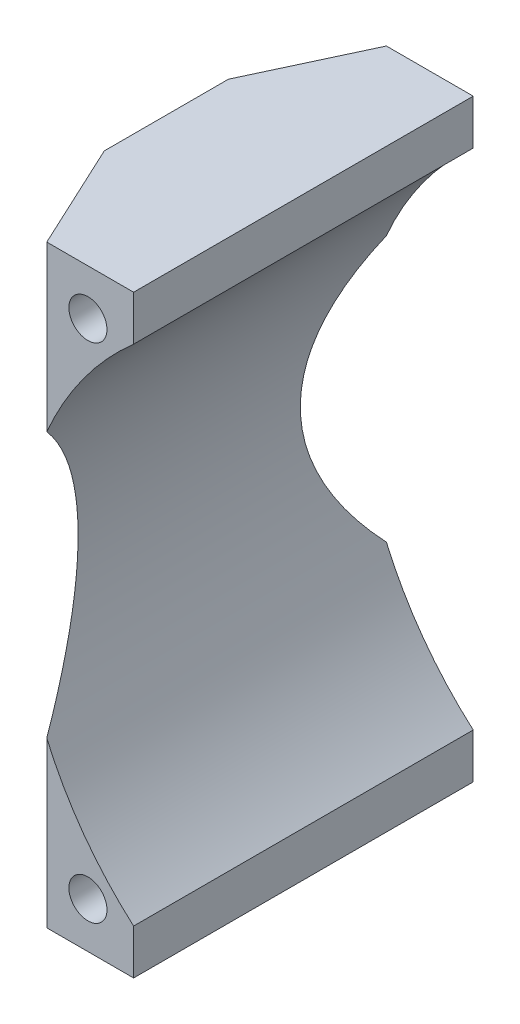
SolidWorks part; units mm, degrees
material "6061-T6 (SS)"
ref_plane "前视基准面" through (0, 0, 0) normal (0, 0, 1) x (1, 0, 0)
ref_plane "上视基准面" through (0, 0, 0) normal (0, 1, 0) x (1, 0, 0)
ref_plane "右视基准面" through (0, 0, 0) normal (1, 0, 0) x (0, 0, -1)
sketch "草图1" plane through (0, 0, 0) normal (0, 0, 1) x (1, 0, 0)
  line L1 (-8.5, 19.5) -> (0, 19.5)
  line L2 (-8.5, 19.5) -> (-8.5, -19.5)
  line L3 (-8.5, -19.5) -> (0, -19.5)
  line L4 (0, 19.5) -> (0, -19.5)
  dimension "D1" = 39
  dimension "D2" = 8.5
extrude "拉伸1" add sketch "草图1" along normal blind 22.3
sketch "草图2" plane through (0, 0, 22.3) normal (0, 0, 1) x (1, 0, 0)
  line L0 (0, 0) -> (14.5, 0) construction
  line L1 (-7.5, 0) -> (-8.5, 0) construction
  line L2 (-8.5, 19.5) -> (-8.5, -19.5) construction
  circle A0 centre (14.5, 0) radius 22
  dimension "D1" = 44
  dimension "D2" = 14.5
extrude "拉伸2" cut sketch "草图2" against normal up to surface (22.3 mm away) up to face at (-4.25, 0, 0)
chamfer "倒角1" [suppressed] distance 1 angle 45
sketch "草图3" plane through (0, 0, 22.3) normal (0, 0, 1) x (1, 0, 0)
  line L0 (-8.5, 19.5) -> (-8.5, -19.5) construction
  line L1 (-8.5, 9) -> (0, 9)
  line L2 (-8.5, 9) -> (-8.5, -19.5)
  line L3 (-8.5, -19.5) -> (0, -19.5)
  line L4 (0, 9) -> (0, -19.5)
  line L5 (0, -19.5) -> (0, -16.5454) construction
  line L6 (0, 19.5) -> (-8.5, 19.5) construction
  line L7 (-8.5, -19.5) -> (0, -19.5) construction
  dimension "D1" = 10.5
extrude "拉伸3" [suppressed] cut sketch "草图3" against normal up to surface (20.3 mm away)
sketch "草图4" plane through (0, 0, 22.3) normal (0, 0, 1) x (1, 0, 0)
  line L0 (-3, 16.5) -> (-3, 19.5) construction
  line L1 (0, 19.5) -> (-8.5, 19.5) construction
  line L2 (-3, 16.5) -> (-8.5, 16.5) construction
  line L3 (-8.5, 19.5) -> (-8.5, -19.5) construction
  line L4 (-3, 16.5) -> (-3, -16.5) construction
  circle A0 centre (-3, 16.5) radius 1.75
  dimension "D1" = 3.5
  dimension "D2" = 3
  dimension "D3" = 33
  dimension "D4" = 5.5
extrude "拉伸4" [suppressed] cut sketch "草图4" against normal up to surface (16.8 mm away)
hole_wizard "M3 螺纹孔1" positions "3D草图1" profile "草图5" tap size "M3" standard "GB"
sketch3d "3D草图1"
  point P0 (-3, 16.5, 22.3)
sketch "草图5" plane through (-3, 16.5, 22.3) normal (1, 0, 0) x (0, -1, 0)
  line L0 (0, 0) -> (0, 10.2511)
  line L1 (0, 10.2511) -> (1.25, 9.5)
  line L2 (1.25, 9.5) -> (1.25, 0)
  line L5 (1.25, 0) -> (0, 0)
  line L10 (0, 10.2511) -> (-1.25, 9.5) construction
  line L11 (0, -6.35) -> (0, 107.95) construction
  dimension "螺纹孔钻头直径" = 2.5
  dimension "螺纹孔钻头深度" = 9.5
  dimension "导头角度" = 118
cosmetic thread "孔螺蚊线3" parameters "D1"=8, "D2"=3
hole_wizard "M3 螺纹孔2" positions "3D草图2" profile "草图6" tap size "M3" standard "GB"
sketch3d "3D草图2"
  point P0 (-3, 16.5, 0)
sketch "草图6" plane through (-3, 16.5, 0) normal (1, 0, 0) x (0, 1, 0)
  line L0 (0, 0) -> (0, 10.2511)
  line L1 (0, 10.2511) -> (1.25, 9.5)
  line L2 (1.25, 9.5) -> (1.25, 0)
  line L5 (1.25, 0) -> (0, 0)
  line L10 (0, 10.2511) -> (-1.25, 9.5) construction
  line L11 (0, -6.35) -> (0, 107.95) construction
  dimension "螺纹孔钻头直径" = 2.5
  dimension "螺纹孔钻头深度" = 9.5
  dimension "导头角度" = 118
cosmetic thread "孔螺蚊线4" parameters "D1"=8, "D2"=3
hole_wizard "M3 螺纹孔3" positions "3D草图3" profile "草图7" tap size "M3" standard "GB"
sketch3d "3D草图3"
  point P0 (-3, -16.5, 22.3)
  point P3 (-3, -16.5, 0)
sketch "草图7" plane through (-3, -16.5, 22.3) normal (1, 0, 0) x (0, -1, 0)
  line L0 (0, 0) -> (0, 10.2511)
  line L1 (0, 10.2511) -> (1.25, 9.5)
  line L2 (1.25, 9.5) -> (1.25, 0)
  line L5 (1.25, 0) -> (0, 0)
  line L10 (0, 10.2511) -> (-1.25, 9.5) construction
  line L11 (0, -6.35) -> (0, 107.95) construction
  dimension "螺纹孔钻头直径" = 2.5
  dimension "螺纹孔钻头深度" = 9.5
  dimension "导头角度" = 118
cosmetic thread "孔螺蚊线5" parameters "D1"=8, "D2"=3
cosmetic thread "孔螺蚊线6" parameters "D1"=8, "D2"=3
chamfer "倒角4" [suppressed] distance 1 angle 45
chamfer "倒角2" distance 6 angle 25 1 edges at (-8.5, 0, 22.3)
chamfer "倒角5" distance 6 angle 25 1 edges at (-8.5, 0, 0)
sketch "草图8" plane through (0, 19.5, 0) normal (0, 1, 0) x (1, 0, 0)
  line L0 (-8.5, -16.3) -> (-8.5, -6) construction
  line L1 (-8.5, -16.3) -> (-8.5, -6)
  line L2 (-9, -15.2277) -> (-9, -7.0723)
  line L3 (-5.7022, 0) -> (-8.5, -6) construction
  line L4 (-8.5, -6) -> (-9, -7.0723)
  line L5 (-8.5, -16.3) -> (-5.7022, -22.3) construction
  line L6 (-9, -15.2277) -> (-8.5, -16.3)
  line L7 (-9, -16.3) -> (-9, -6) construction
  dimension "D1" = 0.5
extrude "拉伸5" add sketch "草图8" against normal up to surface (39 mm away) up to face at (-4.7341, -19.5, 11.15)
